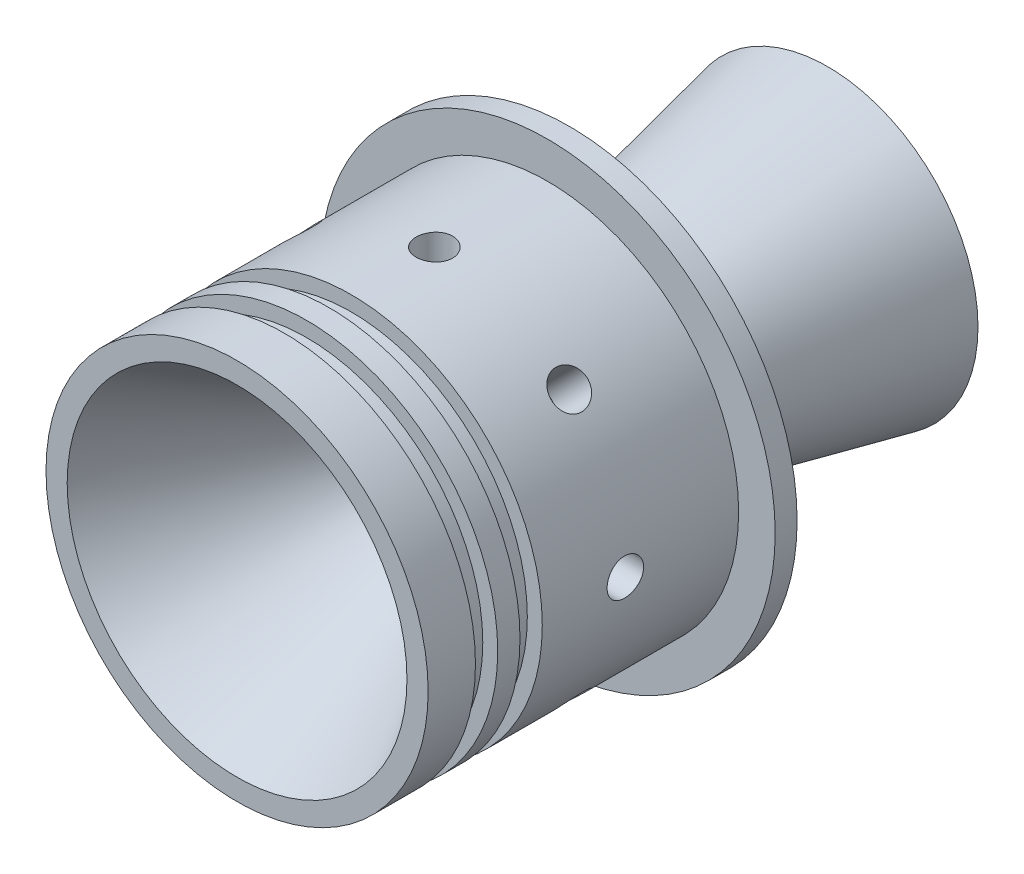
SolidWorks part; units mm, degrees
material "AISI 1045 Steel, cold drawn"
ref_plane "Alzado" through (0, 0, 0) normal (0, 0, 1) x (1, 0, 0)
ref_plane "Planta" through (0, 0, 0) normal (0, 1, 0) x (1, 0, 0)
ref_plane "Vista lateral" through (0, 0, 0) normal (1, 0, 0) x (0, 0, -1)
sketch "Croquis2" plane through (0, 0, 0) normal (1, 0, 0) x (0, 0, -1)
  line L0 (-14.0172, 0) -> (56.1534, 0) construction
  line L1 (0, 23.2509) -> (28.4938, 6.8)
  line L3 (0, 23.2509) -> (0, 26.1493)
  line L4 (0, 26.1493) -> (6.476, 26.1493)
  line L5 (45.4938, 26.1493) -> (45.4938, 13.0554)
  line L7 (80.8333, 20.567) -> (80.8333, 17.5)
  line L8 (6.476, 26.1493) -> (6.476, 24.1044)
  line L9 (6.476, 24.1044) -> (9.524, 24.1044)
  line L10 (9.524, 24.1044) -> (9.524, 26.1493)
  line L11 (9.524, 26.1493) -> (12.572, 26.1493)
  line L13 (30.4938, 6.8) -> (80.8333, 17.5)
  line L15 (45.4938, 13.0554) -> (80.8333, 20.567)
  line L16 (28.4938, 6.8) -> (30.4938, 6.8)
  line L18 (16.3437, 13.8149) -> (19.3157, 12.099) construction
  line L19 (19.0363, 6.8) -> (17.4124, 6.8) construction
  line L20 (19.4766, 6.8) -> (20.8834, 6.8) construction
  line L21 (30.4938, 8.6894) -> (30.4938, -5.1194) construction
  line L22 (12.572, 26.1493) -> (12.572, 24.1044)
  line L23 (12.572, 24.1044) -> (15.62, 24.1044)
  line L24 (15.62, 24.1044) -> (15.62, 26.1493)
  line L25 (15.62, 26.1493) -> (42.4938, 26.1493)
  line L26 (45.4938, 26.1493) -> (45.4938, 31.1493)
  line L27 (45.4938, 31.1493) -> (42.4938, 31.1493)
  line L28 (42.4938, 31.1493) -> (42.4938, 26.1493)
  point P14 (8, 24.1044)
  point P15 (26.9938, 26.1493)
  dimension "D2" = 30
  dimension "D4" = 46.5018
  dimension "D5" = 35
  dimension "D7" = 52.2986
  dimension "D8" = 8
  dimension "D11" = 18.5
  dimension "D13" = 12
  dimension "D9" = 2.0449
  dimension "D10" = 3.048
  dimension "D3" = 13.6
  dimension "D6" = 2
  dimension "D14" = 41.134
  dimension "D12" = 3
  dimension "D15" = 15
  dimension "D16" = 3
  dimension "D17" = 5
revolve "Revolución1" add sketch "Croquis2" angle 360 about L0
ref_plane "Plano1" through (0, 26.1493, 0) normal (0, 1, 0) x (1, 0, 0)
sketch "Croquis3" plane through (0, 26.1493, 0) normal (0, 1, 0) x (1, 0, 0)
  line L0 (26.1493, 45.4938) -> (-26.1493, 45.4938) construction
  point P0 (0, 26.9938)
  dimension "D1" = 18.5
hole_wizard "Ø5.0mm Dowel Hole1" positions "Croquis3" profile "Croquis5" hole size "Ø5.0" standard "ANSI Metric"
sketch "Croquis5" plane through (0, 26.1493, -26.9938) normal (1, 0, 0) x (0, 0, 1)
  line L0 (0, 0) -> (0, 8.5022)
  line L1 (0, 8.5022) -> (2.5, 7)
  line L2 (2.5, 7) -> (2.5, 0)
  line L5 (2.5, 0) -> (0, 0)
  line L10 (0, 8.5022) -> (-2.5, 7) construction
  line L11 (0, -6.35) -> (0, 107.95) construction
  dimension "Diámetro de taladro" = 5
  dimension "Profundidad de taladro" = 7
  dimension "Ángulo de perforador" = 118
pattern_circular "MatrizC1" count 8 over 360 about axis through (0, 0, -15.62) along (0, 0, 1) of "Ø5.0mm Dowel Hole1"
equation "\"Dexit\"=35"
equation "\"D5@Croquis2\"=\"Dexit\""
equation "\"IDCase\"= 52.5018"
equation "\"D7@Croquis2\"=\"IDCaseReal\""
equation "\"RadialClearance\" = 0.004in"
equation "\"IDCaseReal\"= \"IDCase\" - \"RadialClearance\" * 2"
equation "\"OringXlocation\"=8"
equation "\"D8@Croquis2\"=\"OringXlocation\""
equation "\"G\" = 3.05mm'O-ring widht gland 0.12<G<0.125 in"
equation "\"D\" = 2.03mm'O-ring depth gland 0.08<D<0.084 in"
equation "\"ScrewXlocation\"= 15 + 3.5'Location plus radius screw M7"
equation "\"D11@Croquis2\"=\"ScrewXlocation\""
equation "\"NozzleBellThickness\"= 3"
equation "\"D1@Croquis3\"=\"ScrewXlocation\""
equation "\"DnozzleThroat\"= 13.6"
equation "\"LengthNozzleThroat\"=2"
equation "\"OuterNozzleBellThickness\"=2"
equation "\"DivergenceAngle\"=12"
equation "\"D13@Croquis2\"=\"DivergenceAngle\""
equation "\"ConvergenceAngle\"=30"
equation "\"D2@Croquis2\"=\"ConvergenceAngle\""
equation "\"ConvergenceThroatRadius\"= 3"
equation "\"DivergenceThroatRadius\"=5"
equation "\"Dchamber\"= \"IDCase\" - 2 * \"AblativeThickness\""
equation "\"D4@Croquis2\"=\"Dchamber\""
equation "\"AblativeThickness\"= 3mm"
equation "\"D3@Croquis2\"=\"DnozzleThroat\""
equation "\"D6@Croquis2\"=\"LengthNozzleThroat\""
equation "\"D12@Croquis2\"=\"NozzleBellThickness\""
